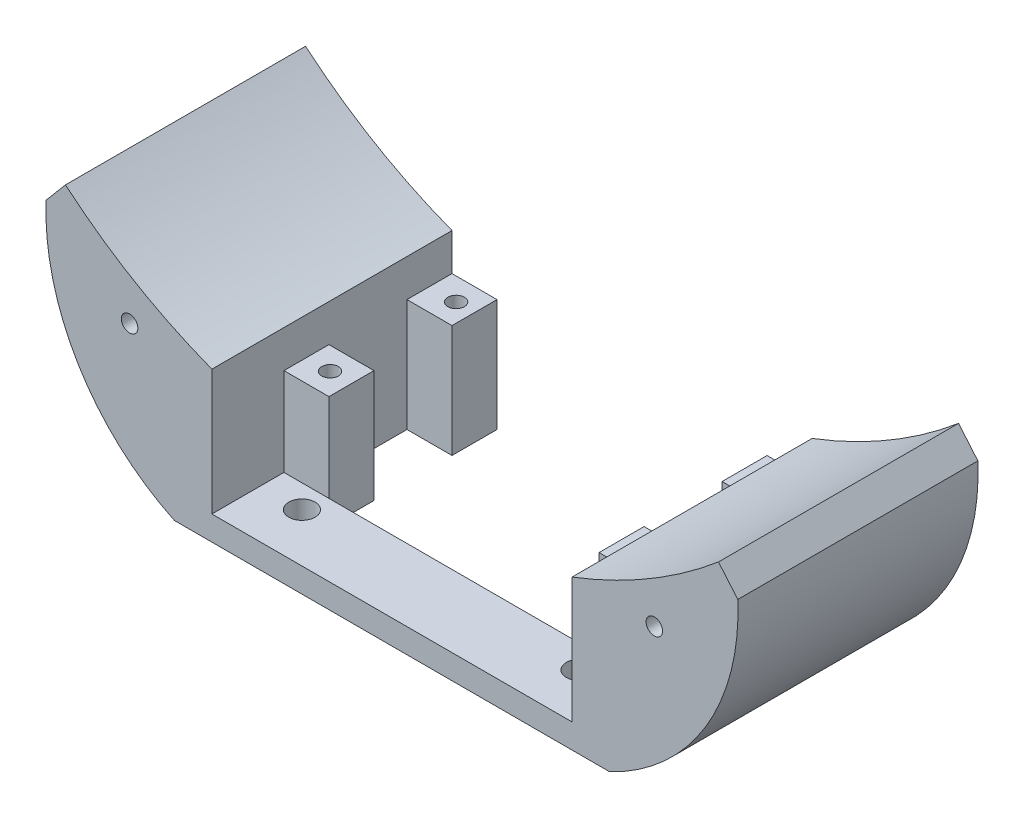
SolidWorks part; units mm, degrees
ref_plane "Płaszczyzna przednia" through (0, 0, 0) normal (0, 0, 1) x (1, 0, 0)
ref_plane "Płaszczyzna górna" through (0, 0, 0) normal (0, 1, 0) x (1, 0, 0)
ref_plane "Płaszczyzna prawa" through (0, 0, 0) normal (1, 0, 0) x (0, 0, -1)
sketch "Szkic1" plane through (0, 0, 0) normal (0, 0, 1) x (1, 0, 0)
  line L0 (2328.7936, 893.0518) -> (2270.7936, 893.0518)
  line L1 (2323.7936, 908.0518) -> (2323.7936, 913.0241)
  line L2 (2323.7936, 908.0518) -> (2275.7936, 908.0518)
  line L3 (2275.7936, 908.0518) -> (2275.7936, 913.0226)
  line L4 (2345.8853, 921.484) -> (2343.3141, 924.5286)
  line L5 (2347.2765, 920.0929) -> (2351.9434, 915.426) construction
  line L6 (2253.6981, 921.484) -> (2256.2693, 924.5286)
  arc A0 (2345.8853, 921.484) -> (2328.7936, 893.0518) centre (2315.9151, 920.1469) cw
  arc A1 (2252.0948, 928.366) -> (2347.4886, 928.366) centre (2299.7917, 976.0629) ccw construction
  arc A2 (2343.3141, 924.5286) -> (2323.7936, 913.0241) centre (2299.7917, 976.0629) cw
  arc A3 (2270.7936, 893.0518) -> (2253.6981, 921.484) centre (2283.6684, 920.1487) cw
  arc A4 (2256.2693, 924.5286) -> (2275.7936, 913.0226) centre (2299.7917, 976.0629) ccw
extrude "Dodanie-wyciągnięcie1" add sketch "Szkic1" along normal blind 32
sketch "Szkic2" plane through (0, 0, 32) normal (0, 0, 1) x (1, 0, 0)
  line L0 (2275.7936, 908.0518) -> (2275.7936, 896.3018)
  line L1 (2323.7936, 896.3018) -> (2275.7936, 896.3018)
  line L3 (2323.7936, 908.0518) -> (2323.7936, 896.3018)
  line L4 (2275.7936, 908.0518) -> (2323.7936, 908.0518)
  dimension "D1" = 11.75
extrude "Wytnij-wyciągnięcie3" cut sketch "Szkic2" against normal blind 9.6
sketch "Szkic3" plane through (0, 908.0518, 0) normal (0, 1, 0) x (1, 0, 0)
  line L0 (2323.7936, -16.4) -> (2317.7936, -16.4)
  line L1 (2323.7936, -22.4) -> (2323.7936, 0) construction
  line L2 (2317.7936, -16.4) -> (2317.7936, -22.4)
  line L3 (2317.7936, -22.4) -> (2281.7936, -22.4)
  line L4 (2281.7936, -22.4) -> (2281.7936, -16.4)
  line L5 (2281.7936, -16.4) -> (2275.7936, -16.4)
  line L6 (2275.7936, -22.4) -> (2275.7936, 0) construction
  line L7 (2275.7936, -16.4) -> (2275.7936, -6)
  line L8 (2275.7936, -6) -> (2281.7936, -6)
  line L9 (2281.7936, -6) -> (2281.7936, 0)
  line L10 (2281.7936, 0) -> (2317.7936, 0)
  line L11 (2317.7936, 0) -> (2317.7936, -6)
  line L12 (2317.7936, -6) -> (2323.7936, -6)
  line L13 (2323.7936, -6) -> (2323.7936, -16.4)
  line L14 (2323.7936, 0) -> (2275.7936, 0) construction
  circle A0 centre (2320.0436, -19.4) radius 1.1
  circle A1 centre (2320.4436, -3) radius 1.1
  circle A2 centre (2279.3436, -3) radius 1.1
  circle A3 centre (2278.9436, -19.4) radius 1.1
  dimension "D9" = 3
  dimension "D1" = 6
  dimension "D2" = 6
  dimension "D3" = 3
  dimension "D4" = 6
  dimension "D5" = 6
  dimension "D6" = 3
  dimension "D7" = 6
  dimension "D8" = 6
  dimension "D10" = 3
  dimension "D11" = 16.4
extrude "Wytnij-wyciągnięcie4" cut sketch "Szkic3" against normal through all
sketch "Szkic4" plane through (0, 896.3018, 0) normal (0, 1, 0) x (1, 0, 0)
  circle A0 centre (2318.2936, -25.5) radius 1.75
  circle A1 centre (2281.2936, -25.5) radius 1.75
extrude "Wytnij-wyciągnięcie5" cut sketch "Szkic4" against normal through all
sketch "Szkic5" plane through (0, 0, 32) normal (0, 0, 1) x (1, 0, 0)
  circle A0 centre (2334.7607, 912.8097) radius 1.1
  circle A1 centre (2264.8227, 912.8097) radius 1.1
extrude "Wytnij-wyciągnięcie6" cut sketch "Szkic5" against normal through all
